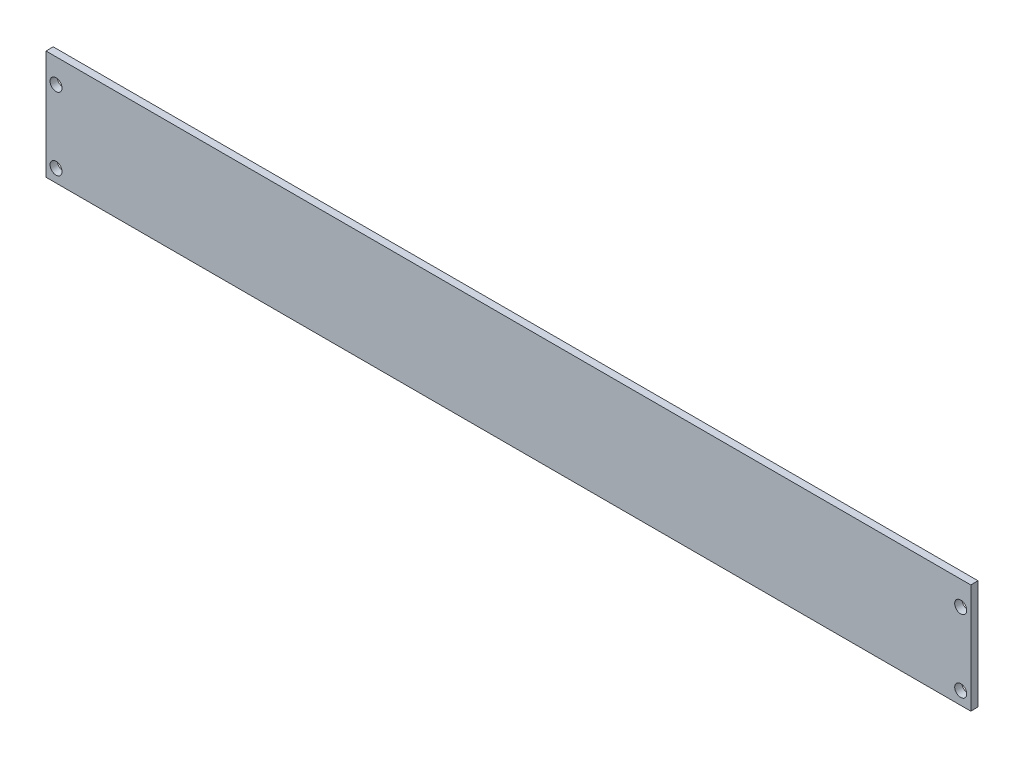
SolidWorks part; units mm, degrees
material "AISI 4130 Steel, normalized at 870C"
ref_plane "Front Plane" through (0, 0, 0) normal (0, 0, 1) x (1, 0, 0)
ref_plane "Top Plane" through (0, 0, 0) normal (0, 1, 0) x (1, 0, 0)
ref_plane "Right Plane" through (0, 0, 0) normal (1, 0, 0) x (0, 0, -1)
sketch "Sketch1" plane through (0, 0, 0) normal (0, 0, 1) x (1, 0, 0)
  line L0 (-142.875, 9.652) -> (-142.875, -13.208) construction
  line L1 (146.05, 17.272) -> (-146.05, 17.272)
  line L2 (146.05, 17.272) -> (146.05, -17.272)
  line L3 (146.05, -17.272) -> (-146.05, -17.272)
  line L4 (-146.05, 17.272) -> (-146.05, -17.272)
  line L5 (146.05, 17.272) -> (-146.05, -17.272) construction
  line L6 (146.05, -17.272) -> (-146.05, 17.272) construction
  line L7 (-142.875, 9.652) -> (142.875, 9.652) construction
  circle A2 centre (-142.875, 9.652) radius 1.8987
  circle A3 centre (-142.875, -13.208) radius 1.8987
  circle A4 centre (142.875, 9.652) radius 1.8987
  circle A5 centre (142.875, -13.208) radius 1.8987
  point P0 (0, 0)
  point P8 (-142.875, -1.778)
  point P15 (0, 9.652)
  dimension "D3" = 3.175
  dimension "D4" = 3.7973
  dimension "D1" = 34.544
  dimension "D2" = 292.1
  dimension "D5" = 7.62
  dimension "D6" = 30.48
extrude "Boss-Extrude1" add sketch "Sketch1" along normal blind 2.286
